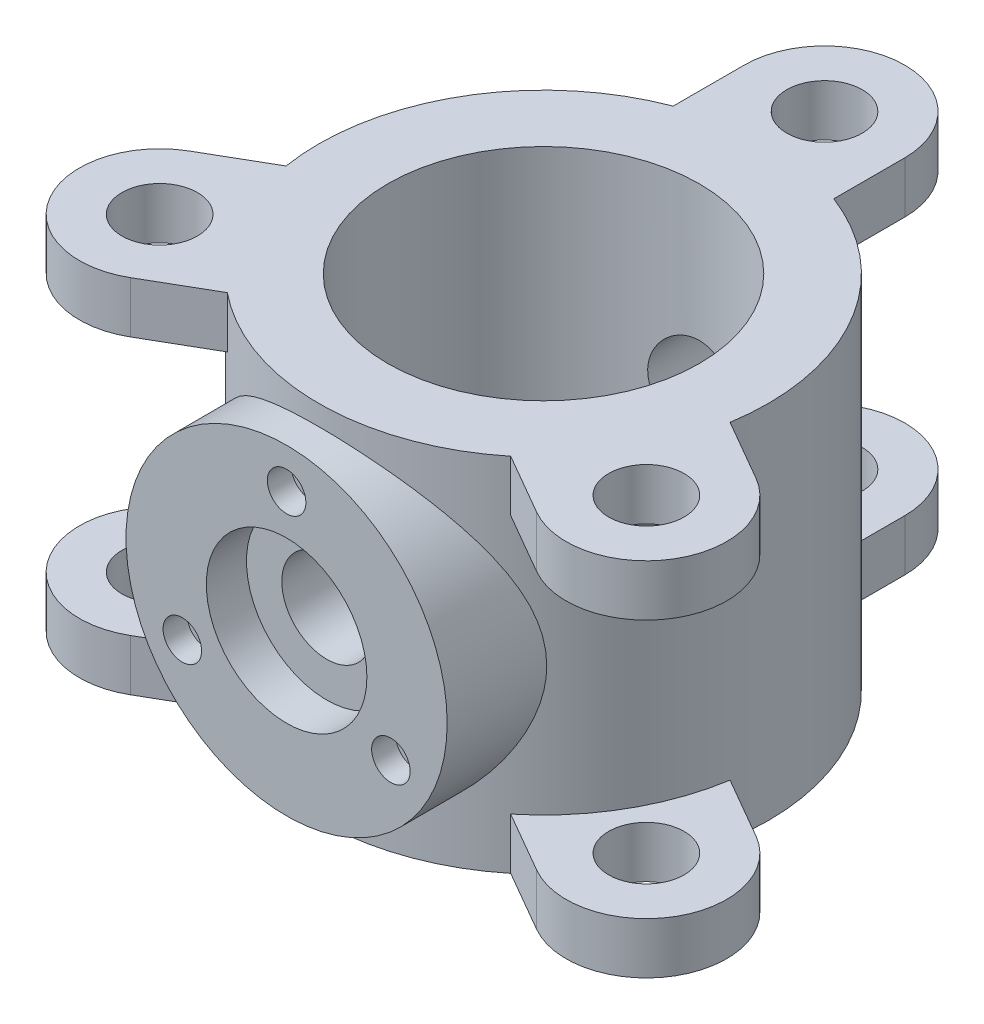
SolidWorks part; units mm, degrees
material "Plain Carbon Steel"
ref_plane "Front Plane" through (0, 0, 0) normal (0, 0, 1) x (1, 0, 0)
ref_plane "Top Plane" through (0, 0, 0) normal (0, 1, 0) x (1, 0, 0)
ref_plane "Right Plane" through (0, 0, 0) normal (1, 0, 0) x (0, 0, -1)
sketch "Sketch1" plane through (0, 0, 0) normal (0, 1, 0) x (1, 0, 0)
  circle A0 centre (0, 0) radius 97
  circle A1 centre (0, 0) radius 140
  dimension "D1" = 280
  dimension "D2" = 194
extrude "Boss-Extrude1" add sketch "Sketch1" along normal mid plane 225
sketch "Sketch2" plane through (0, 112.5, 0) normal (0, 1, 0) x (1, 0, 0)
  line L0 (-50, 175) -> (-50, 130.767)
  line L1 (50, 175) -> (50, 130.767)
  circle A0 centre (0, 175) radius 23.5
  arc A1 (50, 175) -> (-50, 175) centre (0, 175) ccw
  circle A2 centre (0, 0) radius 175 construction
  circle A3 centre (0, 0) radius 140 construction
  arc A4 (50, 130.767) -> (-50, 130.767) centre (0, 0) ccw
  dimension "D1" = 47
  dimension "D2" = 100
  dimension "D3" = 350
extrude "Boss-Extrude2" add sketch "Sketch2" against normal blind 32
pattern_circular "CirPattern1" count 3 over 360 about axis through (0, 112.5, 0) along (0, -1, 0) of "Boss-Extrude2" reverse direction yes
mirror "Mirror1" about plane through (0, 0, 0) normal (0, 1, 0) of "CirPattern1"
ref_plane "Plane1" through (0, 0, 160) normal (0, 0, 1) x (1, 0, 0)
sketch "Sketch3" plane through (0, 0, 160) normal (0, 0, 1) x (1, 0, 0)
  circle A0 centre (0, 0) radius 100
  circle A1 centre (0, 0) radius 50
  circle A2 centre (0, 0) radius 28
  circle A3 centre (0, 0) radius 75 construction
  circle A4 centre (0, 75) radius 12
  circle A5 centre (64.9519, -37.5) radius 12
  circle A6 centre (-64.9519, -37.5) radius 12
  point P9 (-74.8097, -42.1615)
  point P10 (0, 0)
  point P14 (0, 0)
  dimension "D1" = 200
  dimension "D2" = 100
  dimension "D3" = 56
  dimension "D4" = 150
  dimension "D5" = 24
  dimension "D6" = 3
extrude "Boss-Extrude3" add sketch "Sketch3" against normal up to next contours A0
extrude "Cut-Extrude1" cut sketch "Sketch3<4>" against normal blind 25 contours A1
sketch "Sketch3<4>" plane through (0, 0, 160) normal (0, 0, 1) x (1, 0, 0) same geometry as "Sketch3"
extrude "Cut-Extrude2" cut sketch "Sketch3<5>" against normal through all contours A2
sketch "Sketch3<5>" plane through (0, 0, 160) normal (0, 0, 1) x (1, 0, 0) same geometry as "Sketch3"
extrude "Cut-Extrude3" cut sketch "Sketch3<6>" against normal blind 15 contours A4 | A6 | A5
sketch "Sketch3<6>" plane through (0, 0, 160) normal (0, 0, 1) x (1, 0, 0) same geometry as "Sketch3"
